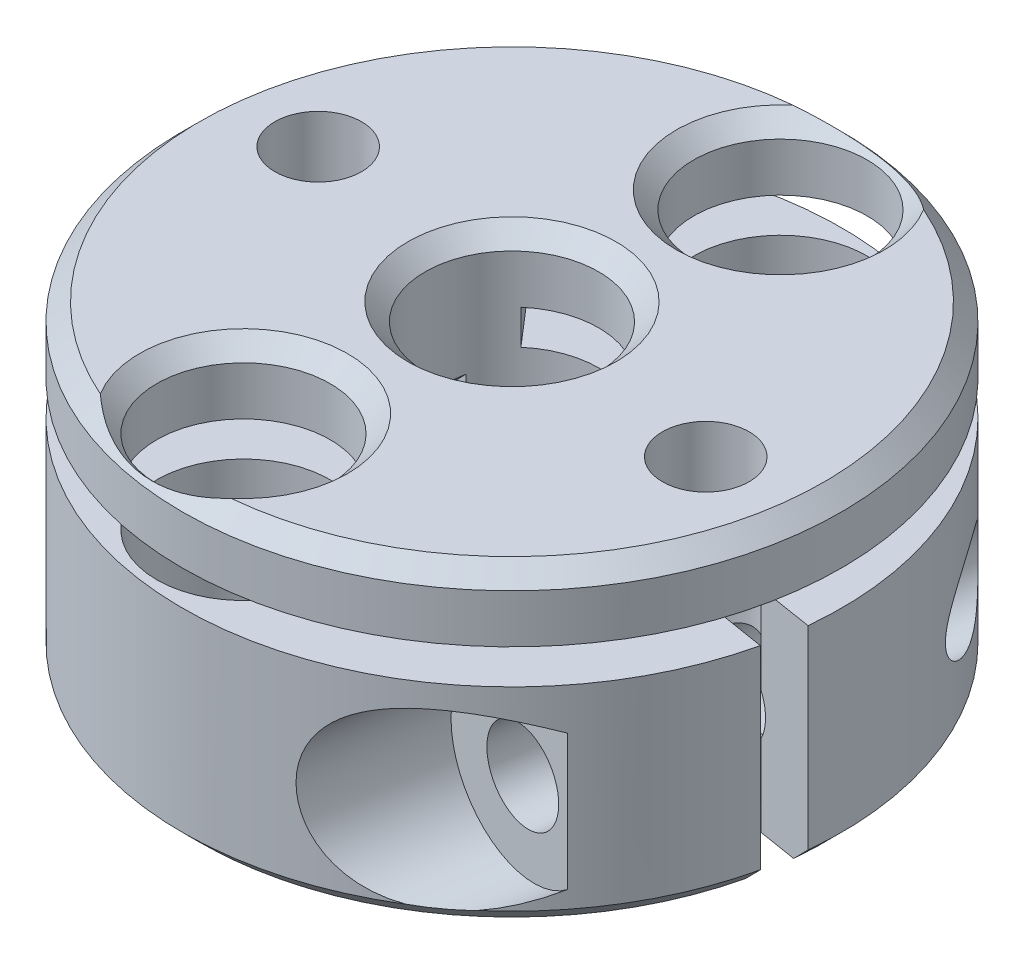
SolidWorks part; units mm, degrees
ref_plane "前视基准面" through (0, 0, 0) normal (0, 0, 1) x (1, 0, 0)
ref_plane "上视基准面" through (0, 0, 0) normal (0, 1, 0) x (1, 0, 0)
ref_plane "右视基准面" through (0, 0, 0) normal (1, 0, 0) x (0, 0, -1)
sketch "草图1" plane through (0, 0, 0) normal (0, 1, 0) x (1, 0, 0)
  circle A0 centre (0, 0) radius 9.5
  dimension "D1" = 19
extrude "凸台-拉伸1" add sketch "草图1" along normal blind 9
sketch "草图2" plane through (0, 9, 0) normal (0, 1, 0) x (1, 0, 0)
  line L0 (-1.3074, 1.5135) -> (-6.2101, 7.1892)
  line L1 (-1.7176, -1.0247) -> (-8.1584, -4.8673)
  circle A0 centre (0, 0) radius 9.5 construction
  arc A1 (-8.1584, -4.8673) -> (-6.2101, 7.1892) centre (0, 0) ccw
  arc A2 (-1.7176, -1.0247) -> (-1.3074, 1.5135) centre (0, 0) ccw
  dimension "D1" = 4
  dimension "D2" = 80
extrude "切除-拉伸1" cut sketch "草图2" against normal blind 1 from offset 1.9 offset against normal yes
sketch "草图3" plane through (0, 9, 0) normal (0, 1, 0) x (1, 0, 0)
  line L0 (-22.1826, 4.1925) -> (25.6659, -3.5398)
  line L1 (25.6659, -3.5398) -> (25.4745, -4.7244)
  line L2 (25.4745, -4.7244) -> (-22.374, 3.0078)
  line L3 (-22.374, 3.0078) -> (-22.1826, 4.1925)
  line L4 (0, 0) -> (0.0957, 0.5923) construction
  line L5 (-6.2101, 7.1892) -> (-1.3074, 1.5135) construction
  line L6 (-6.2101, 7.1892) -> (-1.3074, 1.5135) construction
  dimension "D1" = 1.2
  dimension "D2" = 0.6
  dimension "D3" = 40
extrude "切除-拉伸2" cut sketch "草图3" against normal blind 10 from offset 2 offset against normal yes
sketch "草图4" plane through (-0.0957, 0, 0.5923) normal (0.1595, 0, -0.9872) x (-0.9872, 0, -0.1595)
  line L0 (9.481, 0) -> (9.481, 7.7871)
  line L1 (9.481, 7.7871) -> (0.1939, 7.7871)
  line L2 (0.1939, 7.7871) -> (7.981, 0)
  line L3 (-9.481, 0) -> (9.481, 0) construction
  line L4 (7.981, 0) -> (9.481, 0)
  dimension "D1" = 1.5
  dimension "D2" = 45
extrude "凸台-拉伸2" add sketch "草图4" along normal blind 1.2
sketch "草图5" plane through (0, 9, 0) normal (0, 1, 0) x (1, 0, 0)
  line L0 (-9.2639, 2.1048) -> (-9.4553, 0.9202) construction
  line L1 (-9.2639, 2.1048) -> (-9.4553, 0.9202)
  arc A0 (-9.2639, 2.1048) -> (-9.4553, 0.9202) centre (0, 0) ccw
extrude "凸台-拉伸3" add sketch "草图5" against normal up to surface (9 mm away) up to face at (-2.6263, 0, -0.4244)
sketch "草图6" plane through (0, 9, 0) normal (0, 1, 0) x (1, 0, 0)
  circle A0 centre (0, 0) radius 2.5
  dimension "D1" = 5
extrude "切除-拉伸3" cut sketch "草图6" against normal blind 22.2
sketch "草图7" plane through (0, 0, 0) normal (0, -1, 0) x (1, 0, 0)
  line L0 (0, 0) -> (-1.0768, 6.6636) construction
  line L1 (2.3001, 0.9795) -> (9.2639, 2.1048) construction
  circle A0 centre (-1.0768, 6.6636) radius 2.5
  circle A1 centre (1.0768, -6.6636) radius 2.5
  point P11 (0, 0)
  dimension "D2" = 5
  dimension "D1" = 6.75
  dimension "D3" = 2
extrude "切除-拉伸4" cut sketch "草图7" against normal blind 22.2
sketch "草图8" plane through (0, 0, 0) normal (0, -1, 0) x (1, 0, 0)
  line L0 (-6.6636, -1.0768) -> (0, 0) construction
  line L1 (-7.9745, -0.6809) -> (-2.4916, 0.2051) construction
  circle A0 centre (-6.6636, -1.0768) radius 1.25
  circle A1 centre (6.6636, 1.0768) radius 1.25
  point P11 (0, 0)
  dimension "D1" = 2.5
  dimension "D2" = 6.75
  dimension "D3" = 2
extrude "切除-拉伸5" cut sketch "草图8" against normal blind 22.2
sketch "草图9" plane through (-0.0957, 0, 0.5923) normal (0.1595, 0, -0.9872) x (-0.9872, 0, -0.1595)
  line L0 (-7.8466, 5.7459) -> (-5.6534, 5.7459) construction
  line L2 (-7.8466, 0) -> (-7.8466, 6.1) construction
  line L3 (-5.6534, 6.1) -> (-5.6534, 0) construction
  circle A0 centre (-6.75, 2.9459) radius 1.25
  point P9 (-6.75, 5.7459)
  dimension "D1" = 2.5
  dimension "D2" = 2.8
extrude "切除-拉伸6" cut sketch "草图9" against normal blind 22.2 and the other way blind 22.2
sketch "草图10" plane through (-0.0957, 0, 0.5923) normal (0.1595, 0, -0.9872) x (-0.9872, 0, -0.1595)
  circle A0 centre (-6.75, 2.9459) radius 2.5
  dimension "D1" = 5
extrude "切除-拉伸7" cut sketch "草图10" against normal blind 22.2 from offset 4 offset against normal yes
chamfer "倒角1" distance 0.5 angle 45 9 edges at (-9.3783, 0, -1.5155) (0, 9, 9.5) (1.0768, 0, -9.1636) (0.3988, 0, -2.468) (-0.3988, 0, 2.468) (-1.0768, 0, 4.1636) (-1.0768, 9, 9.1636) (1.0768, 9, -4.1636) (0, 9, 2.5)
